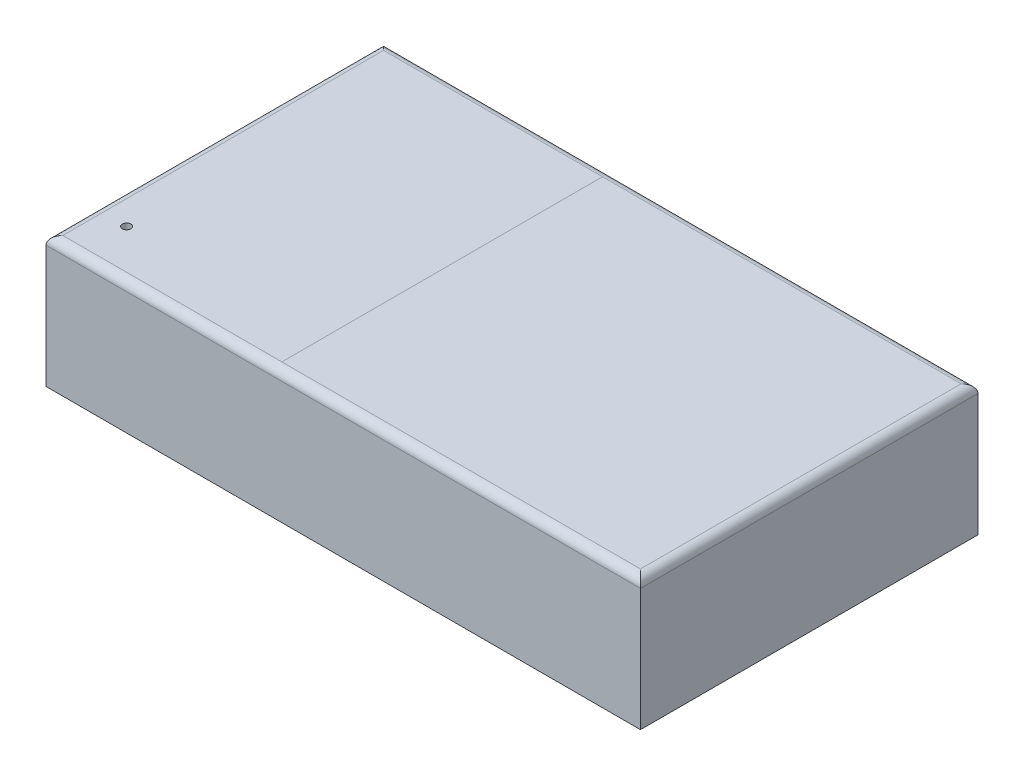
SolidWorks part; units mm, degrees
ref_plane "Front Plane" through (0, 0, 0) normal (0, 0, 1) x (1, 0, 0)
ref_plane "Top Plane" through (0, 0, 0) normal (0, 1, 0) x (1, 0, 0)
ref_plane "Right Plane" through (0, 0, 0) normal (1, 0, 0) x (0, 0, -1)
sketch "Sketch1" plane through (0, 0, 0) normal (0, 1, 0) x (1, 0, 0)
  line L1 (-70.45, -40) -> (70.45, -40)
  line L2 (-70.45, -40) -> (-70.45, 40)
  line L3 (-70.45, 40) -> (70.45, 40)
  line L4 (70.45, -40) -> (70.45, 40)
  line L5 (-70.45, -40) -> (70.45, 40) construction
  line L6 (-70.45, 40) -> (70.45, -40) construction
  point P0 (0, 0)
  dimension "D1" = 80
  dimension "D2" = 140.9
extrude "Boss-Extrude1" add sketch "Sketch1" along normal blind 31
shell "Shell3" thickness 1.5 removed face at (0, 0, 0)
sketch "Sketch4" plane through (-70.45, 0, 0) normal (-1, 0, 0) x (0, 0, 1)
  line L0 (-34.3, 1.6) -> (-28.56, 1.6) construction
  line L1 (-34.3, 3.2) -> (-28.56, 3.2)
  line L2 (-34.3, 0) -> (-28.56, 0)
  arc A0 (-34.3, 3.2) -> (-34.3, 0) centre (-34.3, 1.6) ccw
  arc A1 (-28.56, 0) -> (-28.56, 3.2) centre (-28.56, 1.6) ccw
  point P2 (-31.43, 1.6)
extrude "Cut-Extrude2" cut sketch "Sketch4" against normal blind 1.5
sketch "Sketch6" plane through (-70.45, 0, 0) normal (-1, 0, 0) x (0, 0, 1)
  line L0 (-28.56, 0) -> (40, 0) construction
  line L1 (-24.15, 7.1) -> (-11, 7.1)
  line L2 (-24.15, 7.1) -> (-24.15, 0)
  line L3 (-24.15, 0) -> (-11, 0)
  line L4 (-11, 7.1) -> (-11, 0)
  line L5 (-24.15, 7.1) -> (-11, 0) construction
  line L6 (-24.15, 0) -> (-11, 7.1) construction
  line L7 (-40, 31) -> (-40, 0) construction
  dimension "D1" = 7.1
  dimension "D2" = 13.15
  dimension "D3" = 0
  dimension "D4" = 15.85
extrude "Cut-Extrude3" cut sketch "Sketch6" against normal blind 1.5
sketch "Sketch9" plane through (-70.45, 0, 0) normal (-1, 0, 0) x (0, 0, 1)
  line L0 (-28.56, 0) -> (-24.15, 0) construction
  line L1 (-25.65, 0) -> (-9.5, 0)
  line L2 (-25.65, 0) -> (-25.65, 1.55)
  line L3 (-25.65, 1.55) -> (-9.5, 1.55)
  line L4 (-9.5, 0) -> (-9.5, 1.55)
  line L5 (-11, 0) -> (-11, 7.1) construction
  dimension "D1" = 16.15
  dimension "D2" = 1.55
  dimension "D3" = 1.5
extrude "Boss-Extrude2" add sketch "Sketch9" along normal blind 1.5
sketch "Sketch11" plane through (0, 31, 0) normal (0, 1, 0) x (1, 0, 0)
  circle A0 centre (-62.75, -28.6) radius 1
extrude "Cut-Extrude4" cut sketch "Sketch11" against normal blind 1.5
fillet "Fillet7" radius 2 4 edges at (70.45, 31, 0) (0, 31, 40) (0, 31, -40) (-70.45, 31, 0)
sketch "Sketch16" plane through (0, 31, 0) normal (0, 1, 0) x (1, 0, 0)
  line L0 (68.45, 38) -> (-68.45, 38) construction
  line L1 (68.45, -38) -> (-16.55, -38)
  line L2 (68.45, -38) -> (68.45, 38)
  line L3 (68.45, 38) -> (-16.55, 38)
  line L4 (-16.55, -38) -> (-16.55, 38)
  dimension "D1" = 85
extrude "Cut-Extrude7" cut sketch "Sketch16" against normal through all
extrude "Boss-Extrude6" add sketch "Sketch16<3>" against normal blind 1.5 separate body
sketch "Sketch16<3>" plane through (0, 31, 0) normal (0, 1, 0) x (1, 0, 0) same geometry as "Sketch16"
sketch "Sketch19" plane through (0, 29.5, 0) normal (0, -1, 0) x (-1, 0, 0)
  line L0 (16.55, -1.2795) -> (16.55, -38.5) construction
  line L1 (16.55, -38) -> (16.55, 38) construction
  line L2 (68.95, -38.5) -> (-68.95, -38.5) construction
  line L3 (16.55, -38.5) -> (16.55, 38.5) construction
  line L4 (-68.95, 38.5) -> (68.95, 38.5) construction
  line L6 (16.55, 38.5) -> (18.05, 38.5)
  line L7 (16.55, 38.5) -> (16.55, -38.5)
  line L8 (16.55, -38.5) -> (18.05, -38.5)
  line L9 (18.05, 38.5) -> (18.05, -38.5)
  dimension "D1" = 1.5
extrude "Boss-Extrude7" add sketch "Sketch19" along normal blind 29.5 separate body
